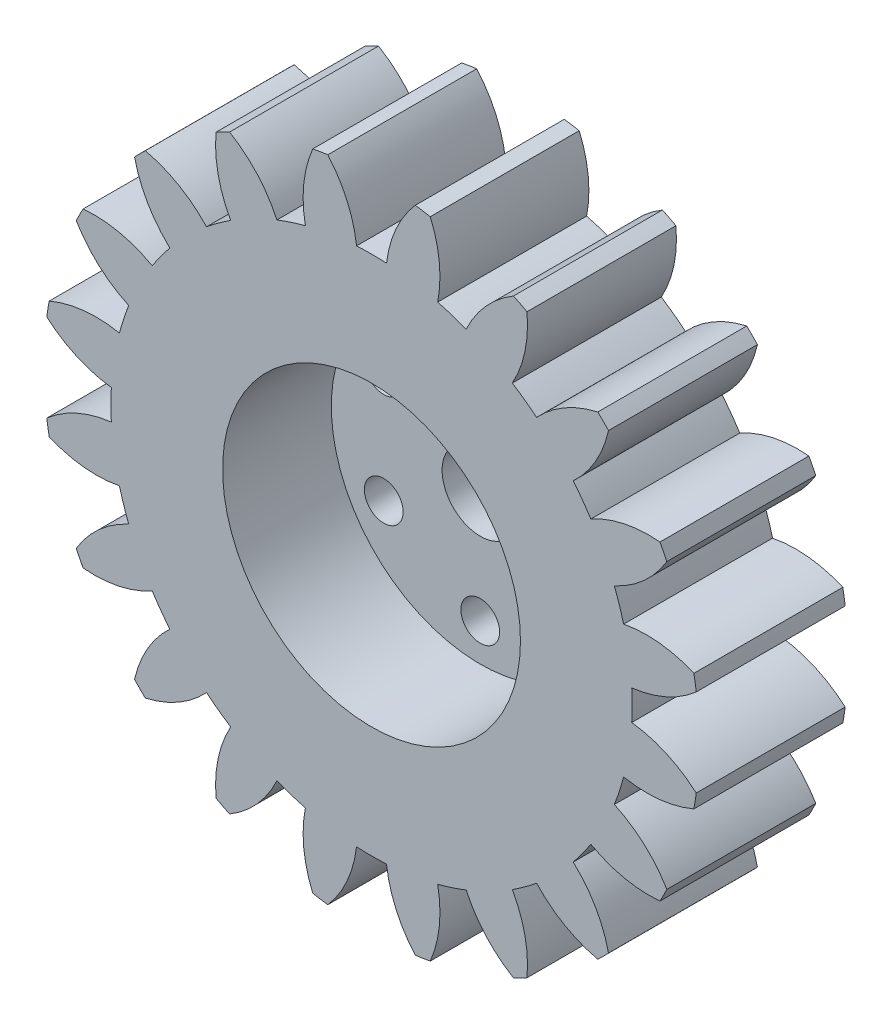
SolidWorks part; units mm, degrees
ref_plane "Front Plane" through (0, 0, 0) normal (0, 0, 1) x (1, 0, 0)
ref_plane "Top Plane" through (0, 0, 0) normal (0, 1, 0) x (1, 0, 0)
ref_plane "Right Plane" through (0, 0, 0) normal (1, 0, 0) x (0, 0, -1)
sketch "Sketch1" plane through (0, 0, 0) normal (0, 0, 1) x (1, 0, 0)
  circle A2 centre (0, 0) radius 3.25
  arc B0 (-27.6898, 3.7307) -> (-22.187, 1.2777) centre (-20.9878, 11.3667) ccw
  arc B1 (-22.187, 1.2777) -> (-22.187, -1.2777) centre (0, 0) ccw
  arc B2 (-22.187, -1.2777) -> (-27.6898, -3.7307) centre (-20.9878, -11.3667) ccw
  arc B3 (-27.6898, -3.7307) -> (-27.4874, -5.0085) centre (0, 0) ccw
  arc B4 (-27.4874, -5.0085) -> (-21.4959, -5.6409) centre (-23.4731, 4.3248) ccw
  arc B5 (-21.4959, -5.6409) -> (-20.7062, -8.0714) centre (0, 0) ccw
  arc B6 (-20.7062, -8.0714) -> (-25.1817, -12.1047) centre (-16.4481, -17.296) ccw
  arc B7 (-25.1817, -12.1047) -> (-24.5944, -13.2575) centre (0, 0) ccw
  arc B8 (-24.5944, -13.2575) -> (-18.7007, -12.0075) centre (-23.6607, -3.1404) ccw
  arc B9 (-18.7007, -12.0075) -> (-17.1986, -14.0749) centre (0, 0) ccw
  arc B10 (-17.1986, -14.0749) -> (-20.2087, -19.2939) centre (-10.2983, -21.5322) ccw
  arc B11 (-20.2087, -19.2939) -> (-19.2939, -20.2087) centre (0, 0) ccw
  arc B12 (-19.2939, -20.2087) -> (-14.0749, -17.1986) centre (-21.5322, -10.2983) ccw
  arc B13 (-14.0749, -17.1986) -> (-12.0075, -18.7007) centre (0, 0) ccw
  arc B14 (-12.0075, -18.7007) -> (-13.2575, -24.5944) centre (-3.1404, -23.6607) ccw
  arc B15 (-13.2575, -24.5944) -> (-12.1047, -25.1817) centre (0, 0) ccw
  arc B16 (-12.1047, -25.1817) -> (-8.0714, -20.7062) centre (-17.296, -16.4481) ccw
  arc B17 (-8.0714, -20.7062) -> (-5.6409, -21.4959) centre (0, 0) ccw
  arc B18 (-5.6409, -21.4959) -> (-5.0085, -27.4874) centre (4.3248, -23.4731) ccw
  arc B19 (-5.0085, -27.4874) -> (-3.7307, -27.6898) centre (0, 0) ccw
  arc B20 (-3.7307, -27.6898) -> (-1.2777, -22.187) centre (-11.3667, -20.9878) ccw
  arc B21 (-1.2777, -22.187) -> (1.2777, -22.187) centre (0, 0) ccw
  arc B22 (1.2777, -22.187) -> (3.7307, -27.6898) centre (11.3667, -20.9878) ccw
  arc B23 (3.7307, -27.6898) -> (5.0085, -27.4874) centre (0, 0) ccw
  arc B24 (5.0085, -27.4874) -> (5.6409, -21.4959) centre (-4.3248, -23.4731) ccw
  arc B25 (5.6409, -21.4959) -> (8.0714, -20.7062) centre (0, 0) ccw
  arc B26 (8.0714, -20.7062) -> (12.1047, -25.1817) centre (17.296, -16.4481) ccw
  arc B27 (12.1047, -25.1817) -> (13.2575, -24.5944) centre (0, 0) ccw
  arc B28 (13.2575, -24.5944) -> (12.0075, -18.7007) centre (3.1404, -23.6607) ccw
  arc B29 (12.0075, -18.7007) -> (14.0749, -17.1986) centre (0, 0) ccw
  arc B30 (14.0749, -17.1986) -> (19.2939, -20.2087) centre (21.5322, -10.2983) ccw
  arc B31 (19.2939, -20.2087) -> (20.2087, -19.2939) centre (0, 0) ccw
  arc B32 (20.2087, -19.2939) -> (17.1986, -14.0749) centre (10.2983, -21.5322) ccw
  arc B33 (17.1986, -14.0749) -> (18.7007, -12.0075) centre (0, 0) ccw
  arc B34 (18.7007, -12.0075) -> (24.5944, -13.2575) centre (23.6607, -3.1404) ccw
  arc B35 (24.5944, -13.2575) -> (25.1817, -12.1047) centre (0, 0) ccw
  arc B36 (25.1817, -12.1047) -> (20.7062, -8.0714) centre (16.4481, -17.296) ccw
  arc B37 (20.7062, -8.0714) -> (21.4959, -5.6409) centre (0, 0) ccw
  arc B38 (21.4959, -5.6409) -> (27.4874, -5.0085) centre (23.4731, 4.3248) ccw
  arc B39 (27.4874, -5.0085) -> (27.6898, -3.7307) centre (0, 0) ccw
  arc B40 (27.6898, -3.7307) -> (22.187, -1.2777) centre (20.9878, -11.3667) ccw
  arc B41 (22.187, -1.2777) -> (22.187, 1.2777) centre (0, 0) ccw
  arc B42 (22.187, 1.2777) -> (27.6898, 3.7307) centre (20.9878, 11.3667) ccw
  arc B43 (27.6898, 3.7307) -> (27.4874, 5.0085) centre (0, 0) ccw
  arc B44 (27.4874, 5.0085) -> (21.4959, 5.6409) centre (23.4731, -4.3248) ccw
  arc B45 (21.4959, 5.6409) -> (20.7062, 8.0714) centre (0, 0) ccw
  arc B46 (20.7062, 8.0714) -> (25.1817, 12.1047) centre (16.4481, 17.296) ccw
  arc B47 (25.1817, 12.1047) -> (24.5944, 13.2575) centre (0, 0) ccw
  arc B48 (24.5944, 13.2575) -> (18.7007, 12.0075) centre (23.6607, 3.1404) ccw
  arc B49 (18.7007, 12.0075) -> (17.1986, 14.0749) centre (0, 0) ccw
  arc B50 (17.1986, 14.0749) -> (20.2087, 19.2939) centre (10.2983, 21.5322) ccw
  arc B51 (20.2087, 19.2939) -> (19.2939, 20.2087) centre (0, 0) ccw
  arc B52 (19.2939, 20.2087) -> (14.0749, 17.1986) centre (21.5322, 10.2983) ccw
  arc B53 (14.0749, 17.1986) -> (12.0075, 18.7007) centre (0, 0) ccw
  arc B54 (12.0075, 18.7007) -> (13.2575, 24.5944) centre (3.1404, 23.6607) ccw
  arc B55 (13.2575, 24.5944) -> (12.1047, 25.1817) centre (0, 0) ccw
  arc B56 (12.1047, 25.1817) -> (8.0714, 20.7062) centre (17.296, 16.4481) ccw
  arc B57 (8.0714, 20.7062) -> (5.6409, 21.4959) centre (0, 0) ccw
  arc B58 (5.6409, 21.4959) -> (5.0085, 27.4874) centre (-4.3248, 23.4731) ccw
  arc B59 (5.0085, 27.4874) -> (3.7307, 27.6898) centre (0, 0) ccw
  arc B60 (3.7307, 27.6898) -> (1.2777, 22.187) centre (11.3667, 20.9878) ccw
  arc B61 (1.2777, 22.187) -> (-1.2777, 22.187) centre (0, 0) ccw
  arc B62 (-1.2777, 22.187) -> (-3.7307, 27.6898) centre (-11.3667, 20.9878) ccw
  arc B63 (-3.7307, 27.6898) -> (-5.0085, 27.4874) centre (0, 0) ccw
  arc B64 (-5.0085, 27.4874) -> (-5.6409, 21.4959) centre (4.3248, 23.4731) ccw
  arc B65 (-5.6409, 21.4959) -> (-8.0714, 20.7062) centre (0, 0) ccw
  arc B66 (-8.0714, 20.7062) -> (-12.1047, 25.1817) centre (-17.296, 16.4481) ccw
  arc B67 (-12.1047, 25.1817) -> (-13.2575, 24.5944) centre (0, 0) ccw
  arc B68 (-13.2575, 24.5944) -> (-12.0075, 18.7007) centre (-3.1404, 23.6607) ccw
  arc B69 (-12.0075, 18.7007) -> (-14.0749, 17.1986) centre (0, 0) ccw
  arc B70 (-14.0749, 17.1986) -> (-19.2939, 20.2087) centre (-21.5322, 10.2983) ccw
  arc B71 (-19.2939, 20.2087) -> (-20.2087, 19.2939) centre (0, 0) ccw
  arc B72 (-20.2087, 19.2939) -> (-17.1986, 14.0749) centre (-10.2983, 21.5322) ccw
  arc B73 (-17.1986, 14.0749) -> (-18.7007, 12.0075) centre (0, 0) ccw
  arc B74 (-18.7007, 12.0075) -> (-24.5944, 13.2575) centre (-23.6607, 3.1404) ccw
  arc B75 (-24.5944, 13.2575) -> (-25.1817, 12.1047) centre (0, 0) ccw
  arc B76 (-25.1817, 12.1047) -> (-20.7062, 8.0714) centre (-16.4481, 17.296) ccw
  arc B77 (-20.7062, 8.0714) -> (-21.4959, 5.6409) centre (0, 0) ccw
  arc B78 (-21.4959, 5.6409) -> (-27.4874, 5.0085) centre (-23.4731, -4.3248) ccw
  arc B79 (-27.4874, 5.0085) -> (-27.6898, 3.7307) centre (0, 0) ccw
  dimension "D1" = 6.5
sketch_block_instance "Arm_Gear-1"
sketch_block "Arm_Gear"
extrude "Boss-Extrude1" add sketch "Sketch1" along normal blind 12.7 contours B78 B79 B0 B1 B2 B3 B4 B5 B6 B7 B8 B9 B10 B11 B12 B13 B14 B15 B16 B17 B18 B19 B20 B21 B22 B23 B24 B25 B26 B27 B28 B29 B30 B31 B32 B33 B34 B35 B36 B37 B38 B39 B40 B41 B42 B43 B44 B45 B46 B47 B48
sketch "Sketch2" plane through (0, 0, 12.7) normal (0, 0, 1) x (1, 0, 0)
  circle A0 centre (0, 0) radius 9.5 construction
  circle A1 centre (0, 9.5) radius 1.651
  circle A2 centre (8.2272, 4.75) radius 1.651
  circle A3 centre (8.2272, -4.75) radius 1.651
  circle A4 centre (0, -9.5) radius 1.651
  circle A5 centre (-8.2272, -4.75) radius 1.651
  circle A6 centre (-8.2272, 4.75) radius 1.651
  point P6 (0, 0)
  point P17 (0, 0)
  dimension "D1" = 19
  dimension "D2" = 3.302
  dimension "D3" = 6
extrude "Cut-Extrude1" cut sketch "Sketch2" against normal up to next
sketch "Sketch3" plane through (0, 0, 12.7) normal (0, 0, 1) x (1, 0, 0)
  circle A0 centre (0, 0) radius 12.7
  dimension "D1" = 25.4
extrude "Cut-Extrude2" cut sketch "Sketch3" against normal blind 9.271
